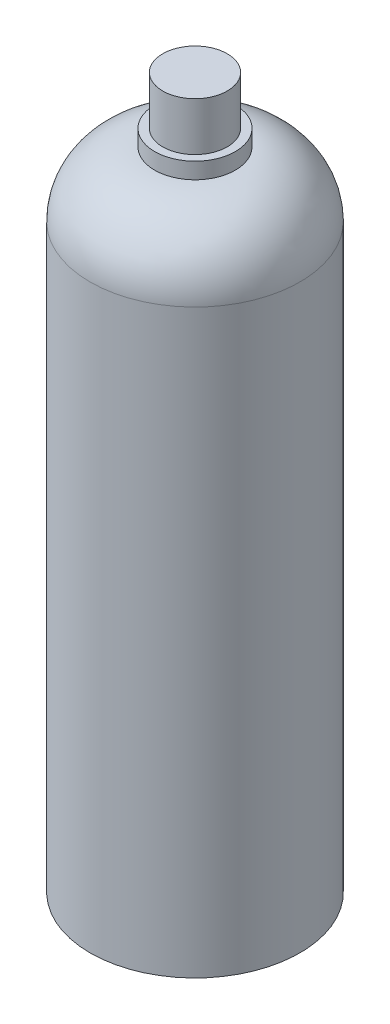
SolidWorks part; units mm, degrees
ref_plane "정면" through (0, 0, 0) normal (0, 0, 1) x (1, 0, 0)
ref_plane "윗면" through (0, 0, 0) normal (0, 1, 0) x (1, 0, 0)
ref_plane "우측면" through (0, 0, 0) normal (1, 0, 0) x (0, 0, -1)
sketch "스케치1" plane through (0, 0, 0) normal (0, 1, 0) x (1, 0, 0)
  circle A0 centre (0, 0) radius 32.5
  dimension "D1" = 65
extrude "보스-돌출1" add sketch "스케치1" along normal blind 200
fillet "필렛1" radius 20 1 edges at (0, 200, 32.5)
sketch "스케치2" plane through (0, 200, 0) normal (0, 1, 0) x (1, 0, 0)
  circle A0 centre (0, 0) radius 10
  circle A1 centre (0, 0) radius 12.5 construction
  circle A2 centre (0, 0) radius 12.5
  dimension "D1" = 20
extrude "보스-돌출2" add sketch "스케치2" along normal blind 20 contours A0
sketch "스케치3" plane through (0, 0, 0) normal (0, 0, 1) x (1, 0, 0)
  line L0 (10, 220) -> (-10, 220) construction
  circle A0 centre (0, 215) radius 2.5
  point P4 (0, 0)
  dimension "D2" = 5
  dimension "D1" = 5
extrude "컷-돌출1" cut sketch "스케치3" along normal blind 2 from offset 10 offset against normal yes
extrude "보스-돌출3" add sketch "스케치2<3>" along normal blind 5
sketch "스케치2<3>" plane through (0, 200, 0) normal (0, 1, 0) x (1, 0, 0) same geometry as "스케치2"
